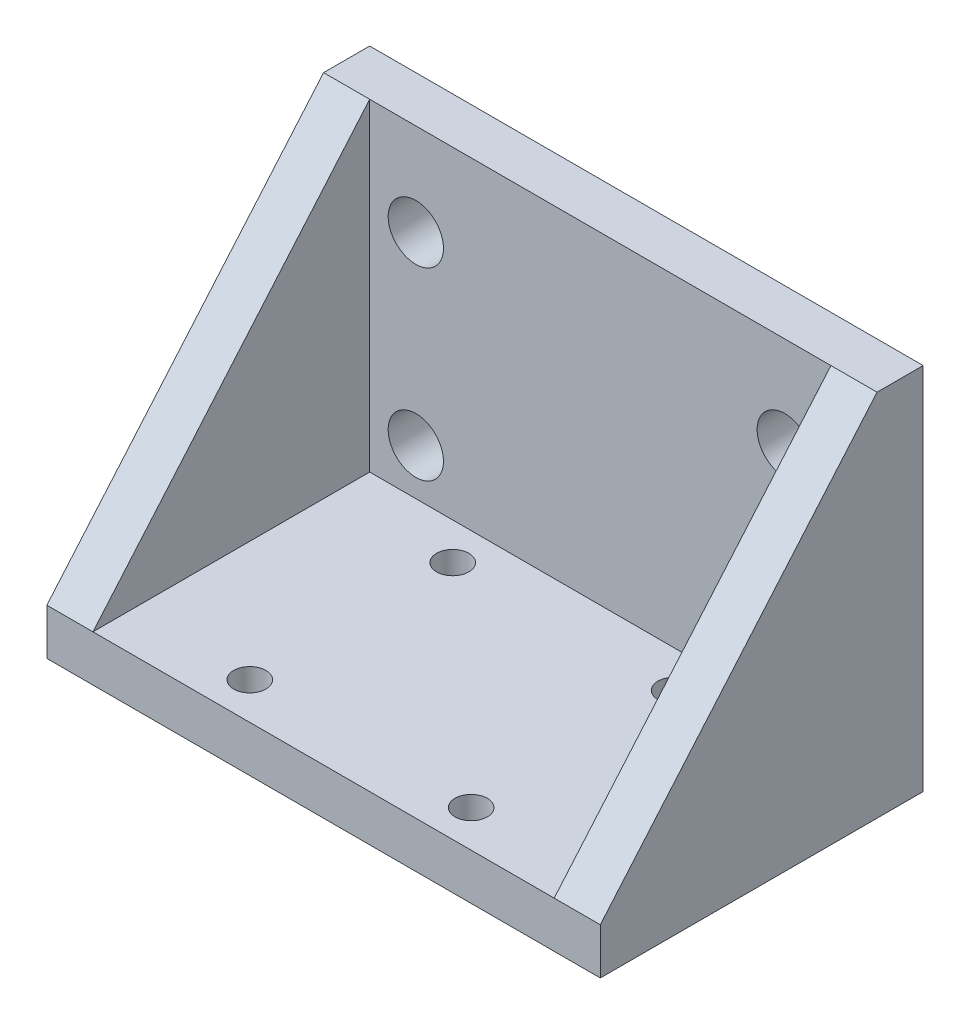
SolidWorks part; units mm, degrees
ref_plane "Спереди" through (0, 0, 0) normal (0, 0, 1) x (1, 0, 0)
ref_plane "Сверху" through (0, 0, 0) normal (0, 1, 0) x (1, 0, 0)
ref_plane "Справа" through (0, 0, 0) normal (1, 0, 0) x (0, 0, -1)
sketch "Эскиз1" plane through (0, 0, 0) normal (0, 1, 0) x (1, 0, 0)
  line L1 (0, 0) -> (60, 0)
  line L2 (0, 0) -> (0, 35)
  line L3 (0, 35) -> (60, 35)
  line L4 (60, 0) -> (60, 35)
  dimension "D1" = 35
  dimension "D2" = 60
extrude "Бобышка-Вытянуть1" add sketch "Эскиз1" along normal blind 5
sketch "Эскиз3" plane through (0, 5, 0) normal (0, 1, 0) x (1, 0, 0)
  line L0 (5, 30) -> (55, 30)
  line L1 (55, 30) -> (55, 0)
  line L2 (0, 0) -> (60, 0) construction
  line L3 (55, 0) -> (60, 0)
  line L4 (60, 0) -> (60, 35)
  line L5 (60, 35) -> (0, 35)
  line L6 (0, 35) -> (0, 0)
  line L7 (0, 0) -> (5, 0)
  line L8 (5, 0) -> (5, 30)
  dimension "D1" = 5
  dimension "D2" = 5
  dimension "D3" = 5
  dimension "D4" = 30
extrude "Бобышка-Вытянуть2" add sketch "Эскиз3" along normal blind 35
sketch "Эскиз4" plane through (0, 0, -35) normal (0, 0, -1) x (-1, 0, 0)
  line L0 (-30, 0) -> (-30, 40) construction
  line L1 (-60, 0) -> (0, 0) construction
  line L2 (-60, 40) -> (0, 40) construction
  line L3 (0, 10) -> (-60, 10) construction
  line L4 (0, 40) -> (0, 0) construction
  line L5 (-60, 40) -> (-60, 0) construction
  line L6 (-60, 30) -> (0, 30) construction
  line L7 (-60, 40) -> (-60, 0) construction
  circle A0 centre (-10, 10) radius 3
  circle A1 centre (-10, 30) radius 3
  circle A2 centre (-50, 30) radius 3
  circle A3 centre (-50, 10) radius 3
  dimension "D3" = 6
  dimension "D1" = 10
  dimension "D2" = 10
  dimension "D4" = 10
  dimension "D5" = 10
extrude "Вырез-Вытянуть1" cut sketch "Эскиз4" against normal up to surface (5 mm away) up to face at (30, 22.5, -30)
sketch "Эскиз5" plane through (0, 0, 0) normal (0, -1, 0) x (-1, 0, 0)
  line L0 (-30, 35) -> (-30, 0) construction
  line L1 (-60, 35) -> (0, 35) construction
  line L2 (0, 0) -> (-60, 0) construction
  line L3 (-42, 26) -> (-42, 4) construction
  line L4 (-42, 4) -> (-18, 4) construction
  line L5 (-18, 4) -> (-18, 26) construction
  line L6 (-18, 26) -> (-42, 26) construction
  circle A0 centre (-42, 26) radius 1.75
  circle A1 centre (-18, 26) radius 1.75
  circle A2 centre (-18, 4) radius 1.75
  circle A3 centre (-42, 4) radius 1.75
  point P8 (-30, 26)
  dimension "D3" = 3.5
  dimension "D1" = 22
  dimension "D2" = 24
  dimension "D4" = 9
extrude "Вырез-Вытянуть2" cut sketch "Эскиз5" against normal up to surface (5 mm away) up to face at (30, 5, -15)
sketch "Эскиз6" plane through (60, 0, 0) normal (1, 0, 0) x (0, 0, -1)
  line L0 (30, 40) -> (0, 5)
  line L1 (0, 40) -> (35, 40) construction
  line L2 (0, 40) -> (0, 0) construction
  line L3 (30, 40) -> (0, 40)
  line L4 (0, 40) -> (0, 5)
  line L5 (35, 40) -> (35, 0) construction
  line L6 (0, 0) -> (35, 0) construction
  dimension "D1" = 5
  dimension "D2" = 5
extrude "Вырез-Вытянуть3" cut sketch "Эскиз6" against normal up to surface (60 mm away) up to face at (0, 20, -17.5)
